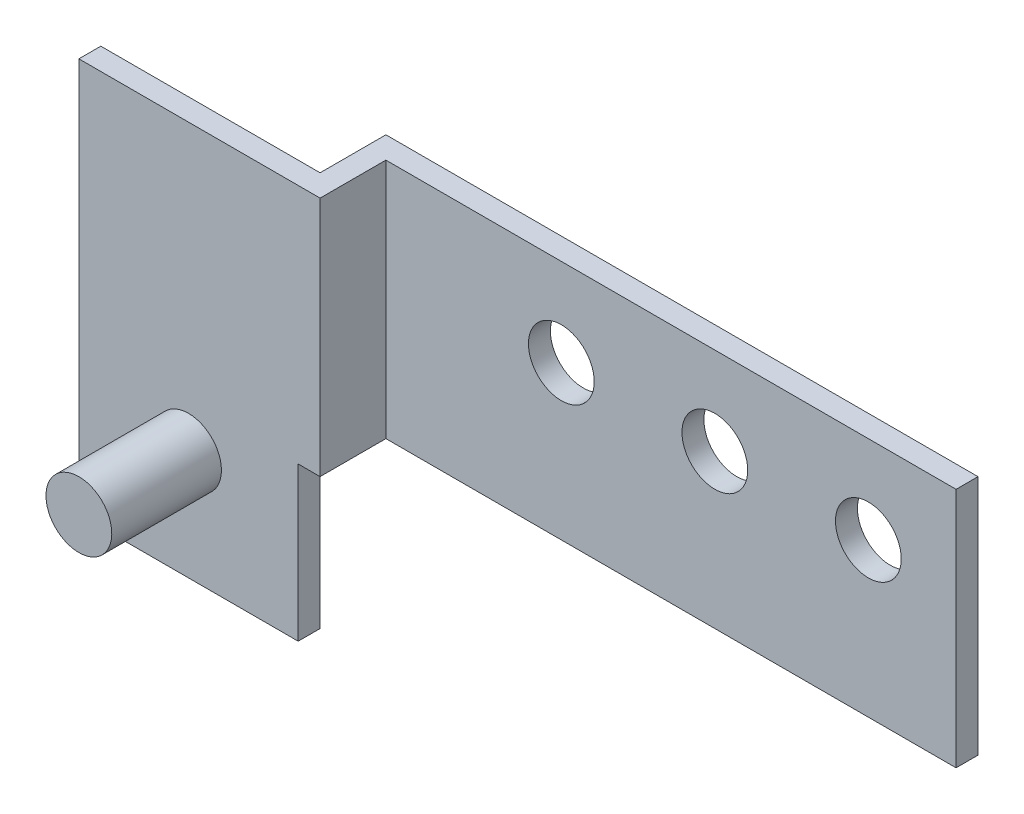
SolidWorks part; units mm, degrees
material "Обычная углеродистая сталь"
ref_plane "Спереди" through (0, 0, 0) normal (0, 0, 1) x (1, 0, 0)
ref_plane "Сверху" through (0, 0, 0) normal (0, 1, 0) x (1, 0, 0)
ref_plane "Справа" through (0, 0, 0) normal (1, 0, 0) x (0, 0, -1)
ref_plane "Плоскость4" through (0, 0, 4) normal (0, 0, 1) x (1, 0, 0)
sketch "Эскиз1" plane through (0, 0, 4) normal (0, 0, 1) x (1, 0, 0)
  line L0 (-10, -18) -> (27, -18)
  line L1 (27, -18) -> (27, 0)
  line L2 (27, 0) -> (-10, 0)
  line L3 (-10, 0) -> (-10, -18)
extrude "Бобышка-Вытянуть1" add sketch "Эскиз1" against normal blind 1
sketch "Эскиз2" plane through (0, 0, 4) normal (0, 0, 1) x (1, 0, 0)
  line L0 (27, -11) -> (0, -11)
  line L1 (0, -11) -> (0, -18)
  line L2 (0, -18) -> (27, -18)
  line L3 (27, -18) -> (27, -11)
extrude "Вырез-Вытянуть1" cut sketch "Эскиз2" against normal through all
sketch "Эскиз3" plane through (0, 0, 3) normal (0, 0, -1) x (-1, 0, 0)
  line L0 (-27, -11) -> (-27, 0)
  line L1 (-27, 0) -> (0, 0)
  line L2 (0, 0) -> (0, -11)
  line L3 (0, -11) -> (-27, -11)
extrude "Бобышка-Вытянуть2" add sketch "Эскиз3" along normal blind 3
sketch "Эскиз4" plane through (0, -11, 0) normal (0, -1, 0) x (1, 0, 0)
  line L0 (1, 4) -> (1, 1)
  line L1 (1, 1) -> (27, 1)
  line L2 (27, 1) -> (27, 4)
  line L3 (27, 4) -> (1, 4)
extrude "Вырез-Вытянуть2" cut sketch "Эскиз4" against normal through all
ref_plane "Плоскость5" through (0, -13, 0) normal (0, -1, 0) x (1, 0, 0)
sketch "Эскиз5" plane through (0, -13, 0) normal (0, -1, 0) x (1, 0, 0)
  line L0 (-3.5, 9) -> (-5, 9)
  line L1 (-5, 9) -> (-5, 4)
  line L2 (-5, 4) -> (-3.5, 4)
  line L3 (-3.5, 4) -> (-3.5, 9)
  line L4 (-5, 9) -> (-5, 4) construction
revolve "Повернуть1" add sketch "Эскиз5" angle 360 about L4 reverse direction yes
hole_wizard "Диаметр отверстия Ø3.0 (3)1" positions "Эскиз7" profile "Эскиз6" hole size "Ø3.0" standard "Ansi Metric"
sketch "Эскиз7" plane through (0, 0, 1) normal (0, 0, 1) x (1, 0, 0)
  point P0 (23, -4)
  point P1 (16, -4)
  point P2 (9, -4)
sketch "Эскиз6" plane through (23, -4, 1) normal (1, 0, 0) x (0, -1, 0)
  line L0 (0, 0) -> (0, 1)
  line L1 (0, 1) -> (1.5, 1)
  line L2 (1.5, 1) -> (1.5, 0)
  line L5 (1.5, 0) -> (0, 0)
  line L11 (0, -6.35) -> (0, 107.95) construction
  dimension "Диаметр сквозного отверстия" = 3
  dimension "Глубина сквозного отверстия" = 1
